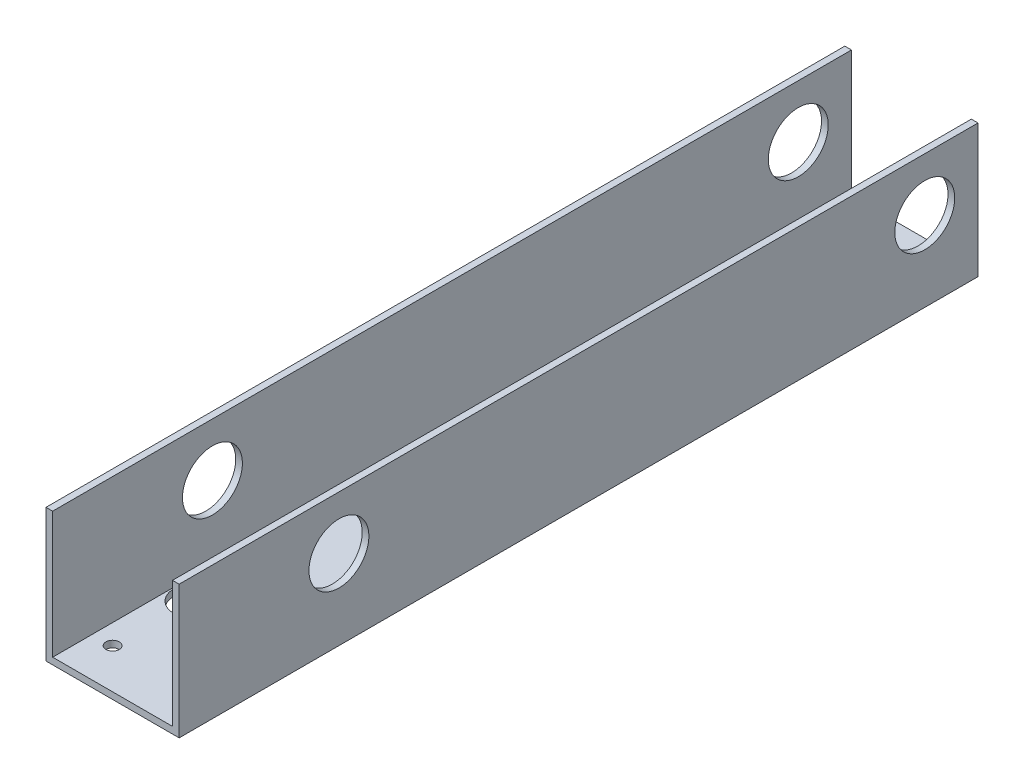
SolidWorks part; units mm, degrees
ref_plane "Front Plane" through (0, 0, 0) normal (0, 0, 1) x (1, 0, 0)
ref_plane "Top Plane" through (0, 0, 0) normal (0, 1, 0) x (1, 0, 0)
ref_plane "Right Plane" through (0, 0, 0) normal (1, 0, 0) x (0, 0, -1)
sketch "Sketch1" plane through (0, 0, 0) normal (0, 0, 1) x (1, 0, 0)
  line L0 (0, 0) -> (63.5, 0)
  line L1 (0, 0) -> (0, 63.5)
  line L2 (0, 63.5) -> (3.175, 63.5)
  line L3 (3.175, 63.5) -> (3.175, 3.175)
  line L4 (3.175, 3.175) -> (60.325, 3.175)
  line L5 (60.325, 3.175) -> (60.325, 63.5)
  line L6 (60.325, 63.5) -> (63.5, 63.5)
  line L7 (63.5, 63.5) -> (63.5, 0)
  dimension "D1" = 63.5
  dimension "D2" = 63.5
  dimension "D3" = 3.175
  dimension "D4" = 3.175
extrude "Boss-Extrude1" add sketch "Sketch1" along normal blind 381
sketch "Sketch2" plane through (0, 0, 0) normal (0, -1, 0) x (1, 0, 0)
  line L0 (12.7, 408.6795) -> (12.7, -26.4569) construction
  line L1 (50.8, 400.8338) -> (50.8, -30.6816) construction
  line L2 (0, 381) -> (0, 0) construction
  line L3 (63.5, 381) -> (63.5, 0) construction
  line L4 (-20.4052, 361.95) -> (91.1096, 361.95) construction
  line L5 (-20.4052, 285.75) -> (86.6681, 285.75) construction
  line L6 (-20.4052, 209.55) -> (103.8411, 209.55) construction
  line L7 (-20.4052, 133.35) -> (112.3217, 133.35) construction
  line L8 (-20.4052, 57.15) -> (106.6564, 57.15) construction
  line L9 (0, 381) -> (63.5, 381) construction
  line L10 (-20.4052, 285.75) -> (-20.4052, 209.55) construction
  line L11 (-20.4052, 209.55) -> (-20.4052, 133.35) construction
  line L12 (-20.4052, 133.35) -> (-20.4052, 57.15) construction
  line L13 (-20.4052, 361.95) -> (-20.4052, 285.75) construction
  circle A0 centre (12.7, 361.95) radius 3.175
  circle A1 centre (50.8, 361.95) radius 3.175
  circle A2 centre (12.7, 285.75) radius 3.175 construction
  circle A3 centre (12.7, 57.15) radius 3.175
  circle A4 centre (12.7, 133.35) radius 3.175
  circle A5 centre (12.7, 209.55) radius 3.175
  point P32 (0, 0)
  point P33 (0, 0)
  point P34 (0, 0)
  point P35 (0, 0)
  point P36 (0, 0)
  point P37 (0, 0)
  point P38 (0, 0)
  point P39 (0, 0)
  point P40 (0, 0)
  point P41 (0, 0)
  point P42 (0, 0)
  point P43 (0, 0)
  point P44 (0, 0)
  point P45 (0, 0)
  dimension "D5" = 6.35
  dimension "D1" = 12.7
  dimension "D2" = 12.7
  dimension "D3" = 19.05
  dimension "D4" = 76.2
extrude "Cut-Extrude1" cut sketch "Sketch2" against normal through all both and the other way through all
sketch "Sketch4" plane through (0, 0, 0) normal (0, -1, 0) x (1, 0, 0)
  line L0 (13.97, 323.85) -> (13.97, 285.75) construction
  line L1 (24.13, 323.85) -> (24.13, 285.75)
  line L2 (3.81, 323.85) -> (3.81, 285.75)
  line L3 (0, 381) -> (0, 0) construction
  line L4 (0, 381) -> (63.5, 381) construction
  arc A0 (24.13, 323.85) -> (3.81, 323.85) centre (13.97, 323.85) ccw
  arc A1 (3.81, 285.75) -> (24.13, 285.75) centre (13.97, 285.75) ccw
  point P2 (13.97, 304.8)
  dimension "D4" = 10.16
  dimension "D1" = 13.97
  dimension "D2" = 57.15
  dimension "D3" = 38.1
extrude "Cut-Extrude3" cut sketch "Sketch4" against normal blind 12.7
ref_axis "Axis1" through (13.97, 3.175, 285.75) along (0, -1, 0)
ref_axis "Axis2" through (13.97, 3.175, 323.85) along (0, -1, 0)
ref_plane "Plane1" through (13.97, 0, 0) normal (-1, 0, 0) x (0, 0, 1)
ref_plane "Plane2" through (0, 0, 285.75) normal (0, 0, -1) x (0, -1, 0)
ref_plane "Plane3" through (0, 0, 323.85) normal (0, 0, -1) x (0, -1, 0)
sketch "Sketch7" plane through (13.97, 0, 0) normal (-1, 0, 0) x (0, 0, 1)
  line L0 (285.75, 0) -> (323.85, 0) construction
  line L1 (381, 0) -> (0, 0) construction
  line L2 (323.85, 1.7462) -> (323.85, -1.7462) construction
  line L3 (285.75, 1.7462) -> (285.75, -1.7462) construction
  line L4 (304.8, 0) -> (304.8, 63.5) construction
  line L5 (381, 63.5) -> (0, 63.5) construction
  circle A0 centre (304.8, 38.1) radius 14.2875
  point P14 (0, 0)
  dimension "D1" = 28.575
  dimension "D2" = 38.1
extrude "Cut-Extrude4" cut sketch "Sketch7" against normal through all both and the other way through all
sketch "Sketch8" plane through (0, 0, 0) normal (0, -1, 0) x (1, 0, 0)
  line L0 (13.97, 323.85) -> (53.975, 323.85) construction
  line L2 (13.97, 285.75) -> (53.975, 285.75) construction
  line L4 (53.975, 285.75) -> (53.975, 323.85) construction
  line L5 (63.5, 381) -> (63.5, 0) construction
  line L6 (38.735, 285.75) -> (38.735, 323.85) construction
  circle A2 centre (38.735, 304.8) radius 3.175
  circle A3 centre (53.975, 316.23) radius 3.175
  circle A4 centre (53.975, 293.37) radius 3.175
  point P19 (53.975, 323.85)
  dimension "D3" = 6.35
  dimension "D1" = 9.525
  dimension "D2" = 15.24
  dimension "D4" = 11.43
  dimension "D5" = 22.86
extrude "Cut-Extrude5" cut sketch "Sketch8" against normal through all both and the other way through all
sketch "Sketch9" plane through (0, 0, 0) normal (-1, 0, 0) x (0, 0, 1)
  line L0 (304.8, 38.1) -> (0, 38.1) construction
  line L1 (0, 63.5) -> (0, 0) construction
  circle A0 centre (25.4, 38.1) radius 14.2875
  point P7 (0, 0)
  dimension "D1" = 28.575
  dimension "D2" = 25.4
extrude "Cut-Extrude6" cut sketch "Sketch9" against normal blind 152.4
